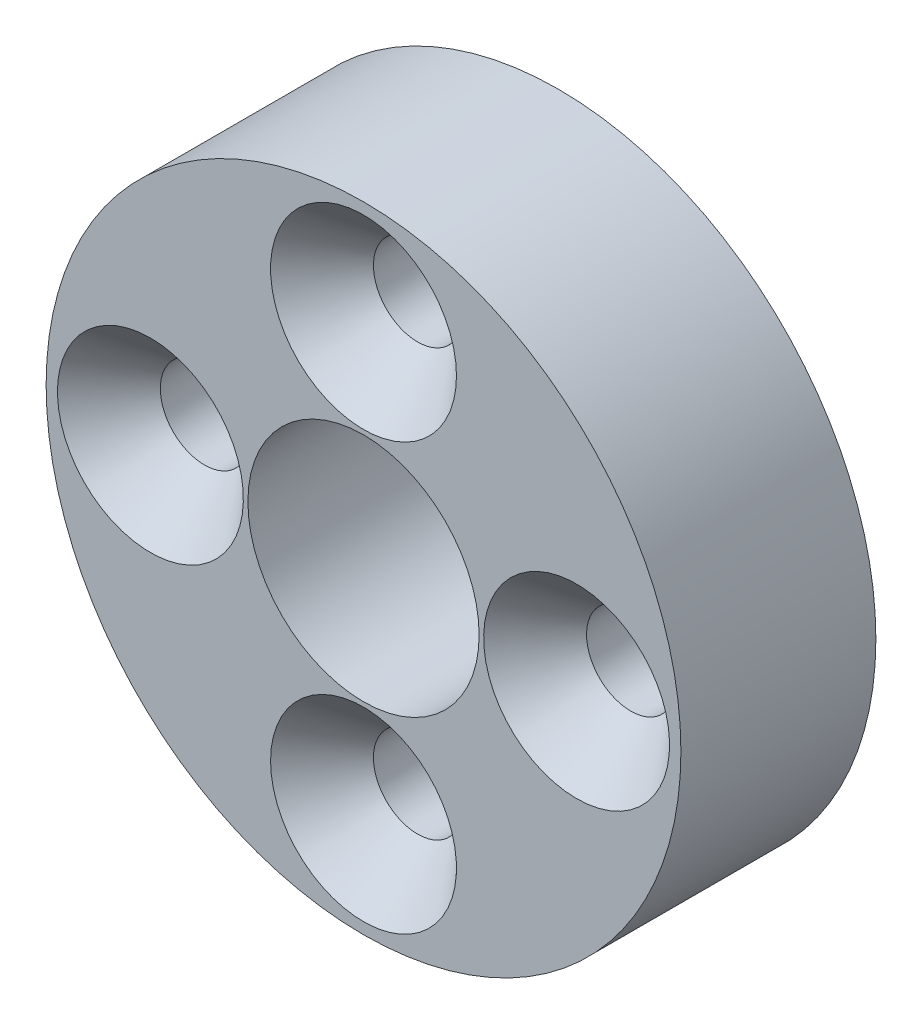
SolidWorks part; units mm, degrees
ref_plane "Front Plane" through (0, 0, 0) normal (0, 0, 1) x (1, 0, 0)
ref_plane "Top Plane" through (0, 0, 0) normal (0, 1, 0) x (1, 0, 0)
ref_plane "Right Plane" through (0, 0, 0) normal (1, 0, 0) x (0, 0, -1)
sketch "Sketch1" plane through (0, 0, 0) normal (0, 0, 1) x (1, 0, 0)
  line L0 (0, 11.938) -> (0, 0) construction
  line L5 (0, 0) -> (11.938, 0) construction
  line L6 (0, -11.938) -> (0, 0) construction
  line L7 (0, 0) -> (-11.938, 0) construction
  circle A0 centre (0, 0) radius 17.78
  circle A1 centre (-11.938, 0) radius 2.4765
  circle A2 centre (0, -11.938) radius 2.4765
  circle A3 centre (11.938, 0) radius 2.4765
  circle A4 centre (0, 11.938) radius 2.4765
  circle A5 centre (0, 0) radius 6.477
  dimension "D1" = 35.56
  dimension "D4" = 4.953
  dimension "D2" = 12.954
  dimension "D3" = 11.938
extrude "Boss-Extrude1" add sketch "Sketch1" along normal blind 10.922
sketch "Sketch2" plane through (0, 0, 0) normal (0, 0, -1) x (-1, 0, 0)
  line L1 (-8.255, -8.255) -> (8.255, -8.255)
  line L2 (-8.255, -8.255) -> (-8.255, 8.255)
  line L3 (-8.255, 8.255) -> (8.255, 8.255)
  line L4 (8.255, -8.255) -> (8.255, 8.255)
  line L5 (-8.255, -8.255) -> (8.255, 8.255) construction
  line L6 (-8.255, 8.255) -> (8.255, -8.255) construction
  circle A0 centre (0, 0) radius 6.477 construction
  circle A1 centre (0, 0) radius 6.477
  point P0 (0, 0)
  dimension "D1" = 16.51
extrude "Boss-Extrude2" add sketch "Sketch2" along normal blind 3.175
sketch "Sketch5" plane through (0, 0, 0) normal (1, 0, 0) x (0, 0, -1)
  line L0 (-10.922, 11.938) -> (0, 11.938) construction
  line L1 (-10.922, 14.4145) -> (-10.922, 9.4615) construction
  line L2 (0, 9.4615) -> (0, 14.4145) construction
  line L3 (-10.922, 11.938) -> (-10.922, 17.145)
  line L4 (-10.922, 17.78) -> (-10.922, -17.78) construction
  line L5 (-10.922, 17.145) -> (-7.62, 14.1719)
  line L6 (-7.62, 14.1719) -> (-7.62, 11.938)
  line L7 (-7.62, 11.938) -> (-10.922, 11.938)
  dimension "D1" = 42
  dimension "D2" = 5.207
  dimension "D3" = 3.302
revolve "Cut-Revolve1" cut sketch "Sketch5" angle 360 about L0
pattern_circular "CirPattern4" count 4 over 360 about axis through (0, 0, 10.922) along (0, 0, 1) of "Cut-Revolve1"
